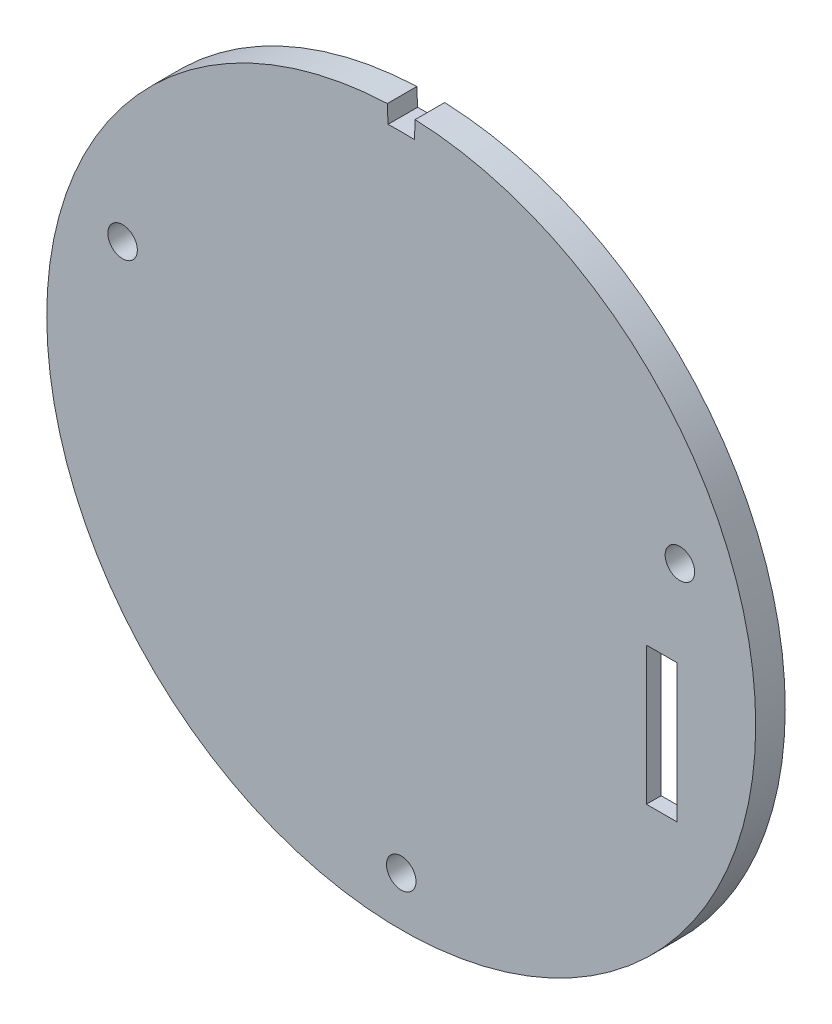
SolidWorks part; units mm, degrees
material "PMMA"
ref_plane "Front Plane" through (0, 0, 0) normal (0, 0, 1) x (1, 0, 0)
ref_plane "Top Plane" through (0, 0, 0) normal (0, 1, 0) x (1, 0, 0)
ref_plane "Right Plane" through (0, 0, 0) normal (1, 0, 0) x (0, 0, -1)
sketch "Sketch1" plane through (0, 0, 0) normal (0, 0, 1) x (1, 0, 0)
  line L0 (0, 45.9969) -> (0, -49.8146) construction
  line L1 (-28, 4.5) -> (28, 4.5)
  line L2 (28, 4.5) -> (28, -17)
  line L3 (28, -17) -> (21.5, -23.5)
  line L4 (21.5, -23.5) -> (-21.5, -23.5)
  line L5 (-21.5, -23.5) -> (-28, -17)
  line L6 (-28, -17) -> (-28, 4.5)
  line L7 (-1.4134, 35.9722) -> (-1.3427, 34.1736)
  line L8 (28, 1.5) -> (24.9, 1.5)
  line L9 (1.3427, 34.1736) -> (1.4134, 35.9722)
  line L10 (24.9, 1.5) -> (24.9, -12.5)
  line L11 (24.9, -12.5) -> (28, -12.5)
  line L12 (28.3, 10.3761) -> (-28.3, 10.3761) construction
  line L14 (23.5, -21.6239) -> (-23.5, -21.6239) construction
  line L15 (23.5, -21.6239) -> (23.5, 25.3761) construction
  line L16 (23.5, 25.3761) -> (-23.5, 25.3761) construction
  line L17 (-23.5, -21.6239) -> (-23.5, 25.3761) construction
  line L18 (23.5, -21.6239) -> (-23.5, 25.3761) construction
  line L19 (23.5, 25.3761) -> (-23.5, -21.6239) construction
  arc A0 (-1.4134, 35.9722) -> (1.4134, 35.9722) centre (0, 0) ccw
  arc A1 (-1.3427, 34.1736) -> (1.3427, 34.1736) centre (0, 0) cw
  circle A2 centre (28.3, 10.3761) radius 1.5
  circle A3 centre (-28.3, 10.3761) radius 1.5
  circle A4 centre (0, -31) radius 1.5
  point P22 (0, 1.8761)
  dimension "D1" = 72
  dimension "D9" = 34.2
  dimension "D10" = 3
  dimension "D13" = 3
  dimension "D14" = 3
  dimension "D18" = 3
  dimension "D19" = 31
  dimension "D2" = 56
  dimension "D3" = 21.5
  dimension "D4" = 135
  dimension "D5" = 28
  dimension "D6" = 135
  dimension "D7" = 4.5
  dimension "D8" = 4.5
  dimension "D11" = 17
  dimension "D12" = 3.1
  dimension "D15" = 47
  dimension "D16" = 47
  dimension "D17" = 15
extrude "Boss-Extrude3" add sketch "Sketch1" against normal blind 3 contours A1 L0 L1 L2 L3 L4 A0 L9 | L0 A1 L7 A0 L4 L5 L6 L1 region at (0, 5.514, 0)
extrude "Boss-Extrude4" add sketch "Sketch1<9>" against normal blind 1.5 contours L1 L0 L4 L3 L2 L11 L10 L8 | L0 L1 L6 L5 L4 region at (-0.7744, -9.2798, 0)
sketch "Sketch1<9>" plane through (0, 0, 0) normal (0, 0, 1) x (1, 0, 0) same geometry as "Sketch1"
